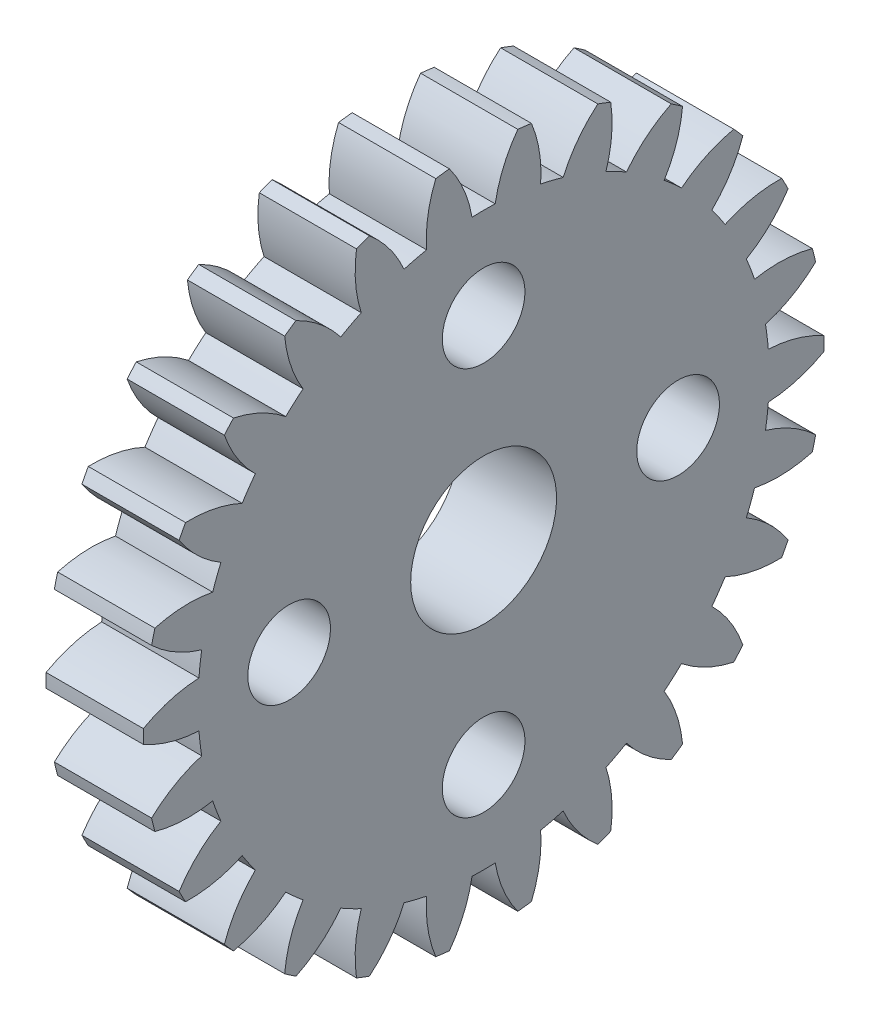
SolidWorks part; units mm, degrees
ref_plane "Plane1" through (0, 0, 0) normal (0, 0, 1) x (1, 0, 0)
ref_plane "Plane2" through (0, 0, 0) normal (0, 1, 0) x (1, 0, 0)
ref_plane "Plane3" through (0, 0, 0) normal (1, 0, 0) x (0, 0, -1)
sketch "HoldingSke" plane through (0, 0, 0) normal (0, 1, 0) x (1, 0, 0)
  line L0 (0, 0) -> (0.8988, -0.4384)
  line L1 (-15, 0) -> (100, 0) construction
  line L2 (0, 0) -> (-2.1039, 2.3779)
  line L3 (0, 0) -> (-11.863, 4.5341)
  line L4 (0, 0) -> (7.762, 3.7858)
  line L5 (0, 0) -> (-46.8476, -17.4728)
  line L6 (0, 0) -> (-3.3159, -2.2372)
  line L7 (-2.1039, 2.3779) -> (8.6586, 51.2059)
  line L8 (-76.2, 54.61) -> (-75.2, 54.61)
  line L9 (-71.009, 38.7566) -> (-53.1078, 45.2721)
  line L10 (-76.2, 71.12) -> (104.1128, 71.12)
  line L11 (0, 0) -> (-4, 0)
  line L12 (-76.2, 101.6) -> (-76.162, 101.6)
  line L13 (24.9733, 27.94) -> (52.9518, 28.4284)
  line L14 (24.9733, 27.94) -> (24.9743, 27.94)
  line L15 (24.9733, 27.94) -> (100.4006, 29.5858)
  line L16 (-63.627, -1) -> (-12.827, -1)
  circle A0 centre (0, 0) radius 3
  circle A1 centre (0, 0) radius 11.749
  circle A2 centre (0, 0) radius 37.5
  circle A3 centre (0, 0) radius 3
  dimension "Num_teeth" = 26
  dimension "Pitch_radius" = 180.3128
  dimension "Width" = 4
  dimension "Thickness" = 4
sketch "BasProSke" plane through (0, 0, 0) normal (0, 1, 0) x (1, 0, 0)
  line L0 (-10, 0) -> (60, 0) construction
  line L1 (0, 0) -> (0, 14)
  line L2 (0, 0) -> (4, 0)
  line L3 (4, 0) -> (4, 14)
  line L4 (4, 14) -> (0, 14)
  dimension "Thickness" = 4
  dimension "Diameter" = 28
revolve "Base-Revolve" add sketch "BasProSke" angle 360 about L0
sketch "TooCutSke" plane through (0, 0, 0) normal (1, 0, 0) x (0, 0, -1)
  line L1 (0, 0) -> (0, 107) construction
  line L2 (0, 0) -> (-0.8514, 12.9721) construction
  line L3 (0, 0) -> (-3.1292, 25.771) construction
  line L4 (-0.8514, 12.9721) -> (-1.5646, 12.8855) construction
  arc A0 (0.477, 11.7393) -> (-0.477, 11.7393) centre (0, 0) ccw
  arc A1 (1.4241, 13.9529) -> (-1.4241, 13.9529) centre (0, 0) ccw
  circle A2 centre (0, 0) radius 13 construction
  circle A3 centre (0, 0) radius 12.216 construction
  arc A4 (-0.477, 11.7393) -> (-1.4241, 13.9529) centre (-5.6014, 10.8561) ccw
  arc A5 (1.4241, 13.9529) -> (0.477, 11.7393) centre (5.6014, 10.8561) ccw
extrude "ToothCut" cut sketch "TooCutSke" along normal through all
fillet "Breaks" [suppressed] radius 0.02 tangent propagation no
fillet "RootFillets" [suppressed] radius 0.251
pattern_circular "TeethCuts" count 26 every 13.846 about axis through (-10, 0, 0) along (1, 0, 0) of "ToothCut", "RootFillets", "Breaks"
sketch "HubNeaOneSke" plane through (0, 0, 0) normal (-1, 0, 0) x (0, 0, 1)
  circle A0 centre (0, 0) radius 11.749
  dimension "Diameter" = 23.498
extrude "HubNearOne" [suppressed] add sketch "HubNeaOneSke" along normal blind 46.0001
sketch "HubNeaBotSke" plane through (0, 0, 0) normal (-1, 0, 0) x (0, 0, 1)
  circle A0 centre (0, 0) radius 11.749
  dimension "Diameter" = 23.498
extrude "HubNearBoth" [suppressed] add sketch "HubNeaBotSke" along normal blind 23
ref_plane "FarPln" through (4, 0, 0) normal (1, 0, 0) x (0, 0, -1)
sketch "HubFarSke" plane through (4, 0, 0) normal (1, 0, 0) x (0, 0, -1)
  circle A0 centre (0, 0) radius 11.749
  dimension "Diameter" = 23.498
extrude "HubFar" [suppressed] add sketch "HubFarSke" along normal blind 23
sketch "BorSke" plane through (0, 0, 0) normal (1, 0, 0) x (0, 0, -1)
  circle A0 centre (0, 0) radius 3
  dimension "Diameter" = 6
extrude "Bore" cut sketch "BorSke" along normal mid plane 100.0001
sketch "KeySke" plane through (0, 0, 0) normal (1, 0, 0) x (0, 0, -1)
  line L0 (-1, 0) -> (-1, 4)
  line L1 (-1, 4) -> (1, 4)
  line L2 (1, 4) -> (1, 0)
  line L3 (0, 0) -> (0, 34) construction
  line L4 (-1, 0) -> (1, 0)
  dimension "Width" = 2
extrude "Keyway" [suppressed] cut sketch "KeySke" along normal mid plane 100.0001
pattern_circular "Keyway2" [suppressed] count 2 every 90 about axis through (-10, 0, 0) along (1, 0, 0) reverse direction yes
hole_wizard "M3 餘隙孔1" positions "Sketch1" profile "Sketch2" hole size "M3" standard "Ansi Metric" end condition through all
sketch "Sketch1" plane through (4, 0, 0) normal (1, 0, 0) x (0, 0, -1)
  line L0 (0, 0) -> (0, 8) construction
  point P2 (0, 8)
  dimension "D1" = 8
sketch "Sketch2" plane through (4, 8, 0) normal (0, 1, 0) x (0, 0, -1)
  line L0 (0, 0) -> (0, 4)
  line L1 (0, 4) -> (1.7, 4)
  line L2 (1.7, 4) -> (1.7, 0)
  line L5 (1.7, 0) -> (0, 0)
  line L11 (0, -6.35) -> (0, 107.95) construction
  dimension "Thru Hole Dia." = 3.4
  dimension "Thru Hole Depth" = 4
pattern_circular "CirPattern1" count 4 over 360 about axis through (50.0001, 0, 0) along (-1, 0, 0) of "M3 餘隙孔1" reverse direction yes
equation "' \"Module@HoldingSke\" = 6.35"
equation "' \"Num_teeth@HoldingSke\" = 12"
equation "' \"Ap@HoldingSke\" =  20"
equation "' \"Ap@HoldingSke\" = 20"
equation "' \"Width@HoldingSke\" = 0.5 * 25.4"
equation "' \"Hub_dia@HoldingSke\"= 1 * 25.4"
equation "' \"Hub_dia@HoldingSke\" = 1 * 25.4"
equation "' \"Overall_len@HoldingSke\" = 1.0 * 25.4"
equation "' \"Bore@HoldingSke\" = 0.75 * 25.4"
equation "' \"T_dim@HoldingSke\" = 0.1 * 25.4"
equation "' \"Width@KeySke\" = 0.25 * 25.4"
equation "' \"Show_teeth@HoldingSke\" = 13"
equation "' \"Backlash@HoldingSke\" = 0.009 * 25.4"
equation "' \"Addendum_fac@HoldingSke\" = 1.0"
equation "' \"Dedendum_fac@HoldingSke\" = 1.25"
equation "' \"Dedendum_add@HoldingSke\" = 0.00005 * 25.4"
equation "' \"Clearance_fac@HoldingSke\" = 0.25"
equation "\"Pitch@HoldingSke\" = 1 / \"Module@HoldingSke\""
equation "\"Overcut_dia@TooCutSke\" = (\"Num_teeth@HoldingSke\" + 2 * \"Addendum_fac@HoldingSke\") / \"Pitch@HoldingSke\" + 0.002 * 25.4"
equation "\"Pitch_dia@TooCutSke\" = \"Num_teeth@HoldingSke\" / \"Pitch@HoldingSke\""
equation "\"Base_dia@TooCutSke\" = \"Num_teeth@HoldingSke\" / \"Pitch@HoldingSke\" * cos((\"Ap@HoldingSke\"  * 3.14159265 / 180))"
equation "\"Root_dia@TooCutSke\" = (\"Num_teeth@HoldingSke\" + 2) / \"Pitch@HoldingSke\" - 2 * (\"Addendum_fac@HoldingSke\" + \"Dedendum_fac@HoldingSke\") / \"Pitch@HoldingSke\" - \"Dedendum_add@HoldingSke\" * 2"
equation "\"Half_ang@TooCutSke\" = 180 / \"Num_teeth@HoldingSke\""
equation "\"Half_CT@TooCutSke\" = \"Num_teeth@HoldingSke\" / \"Pitch@HoldingSke\" * sin((3.14159265 / 2 / \"Num_teeth@HoldingSke\")) / 2 - 7 * \"Backlash@HoldingSke\" / 4"
equation "\"Flank_rad@TooCutSke\" = \"Num_teeth@HoldingSke\" / \"Pitch@HoldingSke\" / 5"
equation "\"Radius@RootFillets\" = \"Clearance_fac@HoldingSke\" / \"Pitch@HoldingSke\" + \"Dedendum_add@HoldingSke\""
equation "\"Break_rad@Breaks\" = 0.02 / \"Pitch@HoldingSke\""
equation "\"Thickness@HoldingSke\" = \"Width@HoldingSke\""
equation "\"OAL@HoldingSke\" = \"Thickness@HoldingSke\""
equation "\"MHD@HoldingSke\" = (\"Num_teeth@HoldingSke\" + 2) / \"Pitch@HoldingSke\" - 2 * (\"Addendum_fac@HoldingSke\" + \"Dedendum_fac@HoldingSke\")  / \"Pitch@HoldingSke\" - \"Dedendum_add@HoldingSke\" * 2"
equation "\"MBD@HoldingSke\" = (\"Num_teeth@HoldingSke\" + 2) / \"Pitch@HoldingSke\" - 2 * (\"Addendum_fac@HoldingSke\" + \"Dedendum_fac@HoldingSke\")  / \"Pitch@HoldingSke\" - \"Dedendum_add@HoldingSke\" * 2 - 0.002 * 25.4"
equation "\"MHD@HoldingSke\" = ((sgn( \"MHD@HoldingSke\" - \"Hub_dia@HoldingSke\" )-1)*( \"MHD@HoldingSke\" - \"Hub_dia@HoldingSke\" ))/-2+ \"Hub_dia@HoldingSke\""
equation "\"MBD@HoldingSke\" = ((sgn( \"MBD@HoldingSke\" - \"Bore@HoldingSke\" )-1)*( \"MBD@HoldingSke\" - \"Bore@HoldingSke\" ))/-2+ \"Bore@HoldingSke\""
equation "\"OAL@HoldingSke\" = ((sgn( \"OAL@HoldingSke\" - \"Overall_len@HoldingSke\" )+1)*( \"OAL@HoldingSke\" - \"Overall_len@HoldingSke\" ))/2 + \"Overall_len@HoldingSke\" + 0.000002 * 25.4"
equation "\"Num_teeth@TeethCuts\" = int( \"Show_teeth@HoldingSke\" ) + 1"
equation "\"Num_teeth@TeethCuts\" = ((sgn( \"Num_teeth@TeethCuts\" - \"Num_teeth@HoldingSke\" )-1)*( \"Num_teeth@TeethCuts\" - \"Num_teeth@HoldingSke\" ))/-2+ \"Num_teeth@HoldingSke\""
equation "\"Num_teeth@TeethCuts\" = ((sgn( \"Num_teeth@TeethCuts\" - 2.0)+1)*( \"Num_teeth@TeethCuts\" - 2.0))/2 +2.0"
equation "\"Angle@TeethCuts\" = 360.0 / \"Num_teeth@HoldingSke\""
equation "\"Diameter@BasProSke\" = (\"Num_teeth@HoldingSke\" + 2 * \"Addendum_fac@HoldingSke\") / \"Pitch@HoldingSke\""
equation "\"Thickness@BasProSke\"  = \"Thickness@HoldingSke\""
equation "' \"Fillet_rad@BasProSke\" =  \"Thickness@HoldingSke\" * 0.05"
equation "' \"Fillet_rad@BasProSke\" = \"Thickness@HoldingSke\" * 0.05"
equation "\"MHD@HoldingSke\" = ((sgn( \"MHD@HoldingSke\" - \"Root_dia@TooCutSke\" )-1)*( \"MHD@HoldingSke\" - \"Root_dia@TooCutSke\" ))/-2+ \"Root_dia@TooCutSke\""
equation "\"Diameter@HubNeaOneSke\" = \"MHD@HoldingSke\""
equation "\"Length@HubNearOne\" = \"OAL@HoldingSke\" - \"Thickness@BasProSke\""
equation "\"Diameter@HubNeaBotSke\" = \"MHD@HoldingSke\""
equation "\"Length@HubNearBoth\" = ( \"OAL@HoldingSke\" - \"Thickness@BasProSke\" ) / 2.0"
equation "\"Thickness@FarPln\" = \"Thickness@BasProSke\""
equation "\"Diameter@HubFarSke\" = \"MHD@HoldingSke\""
equation "\"Length@HubFar\" = ( \"OAL@HoldingSke\" - \"Thickness@BasProSke\" ) / 2.0"
equation "\"Diameter@BorSke\" = \"MBD@HoldingSke\""
equation "\"D1@Bore\" = \"OAL@HoldingSke\" * 2.0"
equation "\"D1@Keyway\" = \"OAL@HoldingSke\" * 2.0"
equation "\"Offset@KeySke\" = \"T_dim@HoldingSke\" + \"MBD@HoldingSke\" / 2.0"
